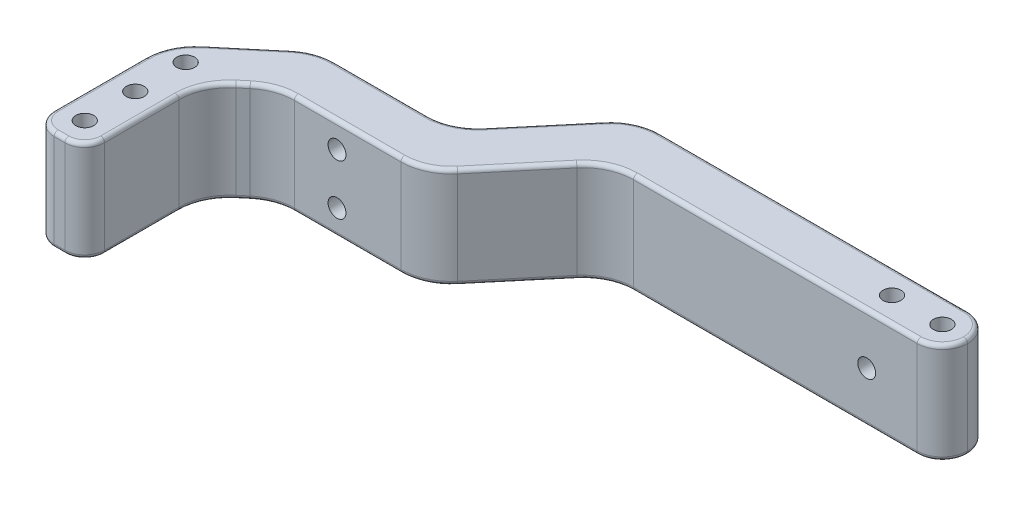
SolidWorks part; units mm, degrees
ref_plane "Front Plane" through (0, 0, 0) normal (0, 0, 1) x (1, 0, 0)
ref_plane "Top Plane" through (0, 0, 0) normal (0, 1, 0) x (1, 0, 0)
ref_plane "Right Plane" through (0, 0, 0) normal (1, 0, 0) x (0, 0, -1)
sketch "Sketch1" plane through (0, 0, 0) normal (0, 1, 0) x (1, 0, 0)
  line L0 (0, 0) -> (0, 38.1) construction
  line L1 (0, 38.1) -> (152.4, 38.1) construction
  line L2 (158.75, 44.45) -> (158.75, 31.75)
  line L3 (158.75, 31.75) -> (6.35, 31.75)
  line L4 (6.35, 31.75) -> (6.35, -6.35)
  line L5 (6.35, -6.35) -> (-6.35, -6.35)
  line L6 (-6.35, -6.35) -> (-6.35, 44.45)
  line L9 (-6.35, 44.45) -> (158.75, 44.45)
  line L10 (6.35, 23.3201) -> (16.3964, 31.75)
  line L11 (-6.35, 27.4799) -> (13.8742, 44.45)
  line L12 (-6.35, 27.4799) -> (6.35, 23.3201) construction
  line L13 (50.8, 38.1) -> (72.1131, 63.5) construction
  line L14 (72.1131, 63.5) -> (152.4, 63.5) construction
  line L15 (69.1521, 69.85) -> (158.75, 69.85)
  line L16 (158.75, 69.85) -> (158.75, 57.15)
  line L17 (158.75, 57.15) -> (75.0742, 57.15)
  line L18 (75.0742, 57.15) -> (64.4176, 44.45)
  line L19 (69.1521, 69.85) -> (47.8389, 44.45)
  line L20 (69.1521, 69.85) -> (75.0742, 57.15) construction
  line L21 (64.4176, 44.45) -> (53.7611, 31.75)
  circle A1 centre (152.4, 38.1) radius 2.25
  circle A2 centre (139.7, 38.1) radius 2.25
  circle A3 centre (0, 25.4) radius 2.25
  circle A4 centre (0, 12.7) radius 2.25
  circle A5 centre (0, 0) radius 2.25
  circle A6 centre (152.4, 63.5) radius 2.25
  circle A7 centre (139.7, 63.5) radius 2.25
  point P0 (0, 0)
  point P35 (0, 0)
  dimension "D3" = 4.5
  dimension "D24" = 4.5
  dimension "D25" = 4.5
  dimension "D1" = 38.1
  dimension "D2" = 152.4
  dimension "D4" = 12.7
  dimension "D6" = 6.35
  dimension "D7" = 6.35
  dimension "D8" = 50
  dimension "D9" = 6.35
  dimension "D10" = 6.35
  dimension "D5" = 6.35
  dimension "D12" = 12.7
  dimension "D13" = 12.7
  dimension "D16" = 6.35
  dimension "D17" = 12.7
  dimension "D18" = 11.35
  dimension "D19" = 25.4
  dimension "D20" = 50
  dimension "D21" = 50.8
  dimension "D22" = 12.7
  dimension "D23" = 12.7
  dimension "D26" = 12.7
extrude "Boss-Extrude1" add sketch "Sketch1" along normal blind 25.4 contours L11 L6 L5 L4 L3 L2 L9 A5 A4 A3 A2 A1 | L4 L10 L3 | L15 L19 L9 L18 L17 L16 A7 A6 region at (58.422, 0, -38.66) region at (102.8656, 0, -61.4649) region at (9.6988, 0, -28.94)
fillet "Fillet2" radius 5 2 edges at (-6.35, 12.7, 6.35) (6.35, 12.7, 6.35)
sketch "Sketch3" plane through (0, 0, -69.85) normal (0, 0, -1) x (-1, 0, 0)
  line L1 (-13.8742, 25.4) -> (-47.8389, 25.4) construction
  circle A0 centre (-31.75, 6.35) radius 2.25
  circle A1 centre (-31.75, 19.05) radius 2.25
  circle A2 centre (-139.7, 12.7) radius 2.25
  dimension "D4" = 4.5
  dimension "D7" = 4.5
  dimension "D1" = 31.75
  dimension "D2" = 12.7
  dimension "D3" = 6.35
  dimension "D5" = 107.95
  dimension "D6" = 12.7
extrude "Cut-Extrude2" cut sketch "Sketch3" against normal through all
fillet "Fillet4" radius 12.7 8 edges at (16.3964, 12.7, -31.75) (6.35, 12.7, -23.3201) (13.8742, 12.7, -44.45) (-6.35, 12.7, -27.4799) (69.1521, 12.7, -69.85) (47.8389, 12.7, -44.45) (75.0742, 12.7, -57.15) (53.7611, 12.7, -31.75)
fillet "Fillet6" radius 6.35 2 edges at (158.75, 12.7, -69.85) (158.75, 12.7, -57.15)
fillet "Fillet5" radius 1 46 edges at (30.2067, 0, -44.45) (14.1529, 0, -43.6841) (4.2599, 0, -36.3827) (-5.1601, 0, -26.925) (-6.35, 0, -10.1039) (-4.8855, 0, 4.8855) (4.8855, 0, 4.8855) (6.35, 0, -8.024) (7.5399, 0, -22.7652) (11.871, 0, -27.9528) (16.6751, 0, -30.9841) (11.871, 25.4, -27.9528) (7.5399, 25.4, -22.7652) (6.35, 25.4, -8.024) (4.8855, 25.4, 4.8855) (-4.8855, 25.4, 4.8855) (-6.35, 25.4, -10.1039) (-5.1601, 25.4, -26.925) (4.2599, 25.4, -36.3827) (14.1529, 25.4, -43.6841) (30.2067, 25.4, -44.45) (34.4289, 25.4, -31.75) (34.4289, 0, -31.75) (16.6751, 25.4, -30.9841) (0, 0, 6.35) (0, 25.4, 6.35) (53.2062, 0, -32.9399) (64.4176, 0, -44.45) (75.629, 0, -55.9601) (116.6981, 0, -57.15) (156.8901, 0, -59.0099) (156.8901, 0, -67.9901) (113.7371, 0, -69.85) (69.7069, 0, -68.6601) (58.4955, 0, -57.15) (47.2841, 0, -45.6399) (47.2841, 25.4, -45.6399) (58.4955, 25.4, -57.15) (69.7069, 25.4, -68.6601) (113.7371, 25.4, -69.85) (156.8901, 25.4, -67.9901) (156.8901, 25.4, -59.0099) (116.6981, 25.4, -57.15) (75.629, 25.4, -55.9601) (64.4176, 25.4, -44.45) (53.2062, 25.4, -32.9399)
